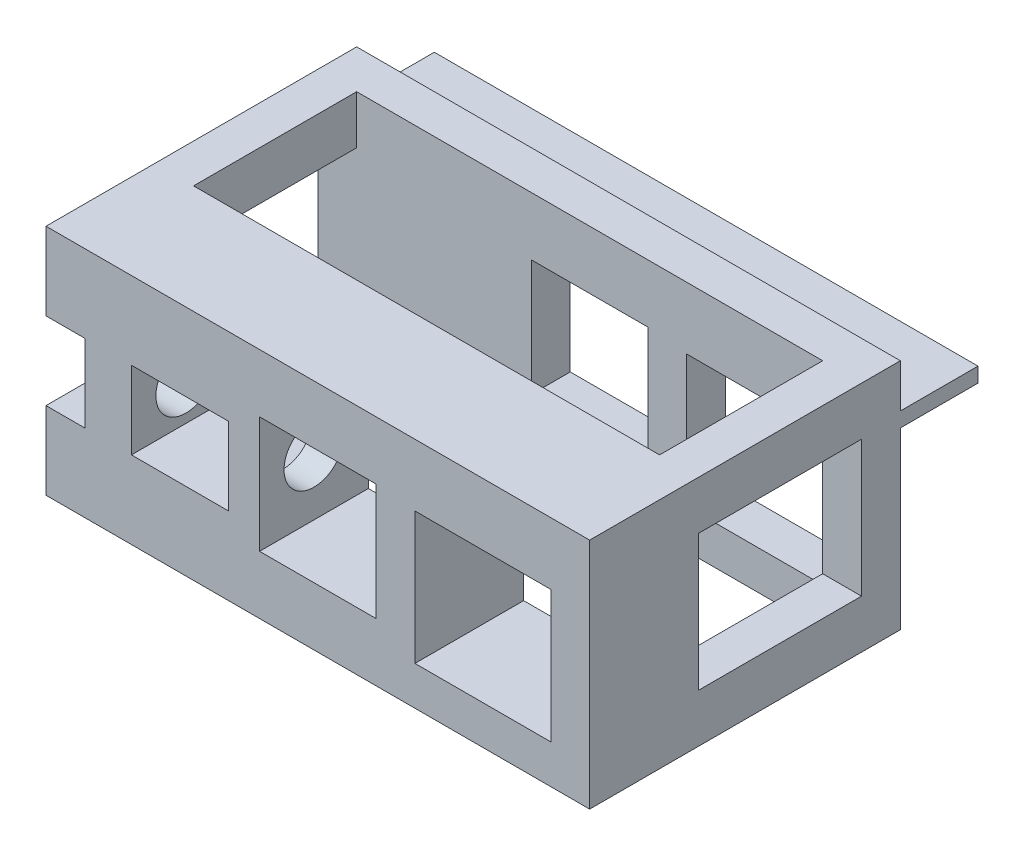
SolidWorks part; units mm, degrees
material "ABS"
ref_plane "Front Plane" through (0, 0, 0) normal (0, 0, 1) x (1, 0, 0)
ref_plane "Top Plane" through (0, 0, 0) normal (0, 1, 0) x (1, 0, 0)
ref_plane "Right Plane" through (0, 0, 0) normal (1, 0, 0) x (0, 0, -1)
sketch "Sketch1" plane through (0, 0, 0) normal (0, 0, 1) x (1, 0, 0)
  line L1 (0, 0) -> (88.9, 0)
  line L2 (0, 0) -> (0, 38.1)
  line L3 (0, 38.1) -> (88.9, 38.1)
  line L4 (88.9, 0) -> (88.9, 38.1)
  dimension "D1" = 88.9
  dimension "D2" = 38.1
extrude "Boss-Extrude1" add sketch "Sketch1" against normal blind 17.78
sketch "Sketch2" plane through (0, 0, 0) normal (0, 0, 1) x (1, 0, 0)
  line L0 (0, 19.05) -> (88.9, 19.05) construction
  line L1 (0, 0) -> (0, 38.1) construction
  line L2 (88.9, 0) -> (88.9, 38.1) construction
  line L3 (44.45, 0) -> (44.45, 38.1) construction
  line L4 (0, 0) -> (88.9, 0) construction
  line L5 (0, 38.1) -> (88.9, 38.1) construction
  line L6 (88.9, 30.1625) -> (82.55, 30.1625)
  line L7 (34.925, 28.575) -> (53.975, 28.575)
  line L8 (34.925, 28.575) -> (34.925, 9.525)
  line L9 (34.925, 9.525) -> (53.975, 9.525)
  line L10 (53.975, 28.575) -> (53.975, 9.525)
  line L11 (0, 39.0525) -> (6.35, 39.0525)
  line L12 (0, 39.0525) -> (0, 30.1625)
  line L13 (0, 30.1625) -> (6.35, 30.1625)
  line L14 (6.35, 39.0525) -> (6.35, 30.1625)
  line L15 (82.55, 39.0525) -> (82.55, 30.1625)
  line L16 (88.9, 39.0525) -> (82.55, 39.0525)
  line L17 (88.9, 39.0525) -> (88.9, 30.1625)
  line L18 (88.9, -0.9525) -> (88.9, 7.9375)
  line L19 (88.9, -0.9525) -> (82.55, -0.9525)
  line L20 (82.55, -0.9525) -> (82.55, 7.9375)
  line L21 (88.9, 7.9375) -> (82.55, 7.9375)
  line L22 (0, 7.9375) -> (6.35, 7.9375)
  line L23 (6.35, -0.9525) -> (6.35, 7.9375)
  line L24 (0, -0.9525) -> (6.35, -0.9525)
  line L25 (0, -0.9525) -> (0, 7.9375)
  line L26 (0, 38.1) -> (0, 0) construction
  line L27 (29.845, 25.4) -> (13.97, 25.4)
  line L28 (29.845, 25.4) -> (29.845, 12.7)
  line L29 (29.845, 12.7) -> (13.97, 12.7)
  line L30 (13.97, 25.4) -> (13.97, 12.7)
  dimension "D1" = 19.05
  dimension "D3" = 34.925
  dimension "D5" = 11.1125
  dimension "D6" = 8.89
  dimension "D7" = 6.35
  dimension "D10" = 12.7
  dimension "D2" = 19.05
  dimension "D4" = 9.525
  dimension "D11" = 6.35
  dimension "D9" = 13.97
  dimension "D8" = 5.08
extrude "Cut-Extrude1" cut sketch "Sketch2" against normal blind 41.402 contours L28 L27 L30 L29 | L8 L7 L10 L9 | L12 L11 L14 L13 | L22 L23 L24 L25 | L18 L21 L20 L19 | L6 L15 L16 L17
ref_plane "Plane1" through (0, 0, -50.8) normal (0, 0, 1) x (1, 0, 0)
sketch "Sketch3" plane through (0, 0, -50.8) normal (0, 0, 1) x (1, 0, 0)
  line L0 (34.925, 9.525) -> (53.975, 9.525) construction
  line L1 (53.975, 9.525) -> (53.975, 28.575) construction
  line L2 (53.975, 28.575) -> (34.925, 28.575) construction
  line L3 (34.925, 28.575) -> (34.925, 9.525) construction
  line L4 (34.925, 9.525) -> (53.975, 9.525)
  line L5 (53.975, 9.525) -> (53.975, 28.575)
  line L6 (53.975, 28.575) -> (34.925, 28.575)
  line L7 (34.925, 28.575) -> (34.925, 9.525)
  line L20 (88.9, 7.9375) -> (88.9, 30.1625)
  line L25 (82.55, 38.1) -> (6.35, 38.1)
  line L26 (0, 30.1625) -> (0, 7.9375)
  line L31 (88.9, 30.1625) -> (82.55, 30.1625)
  line L33 (88.9, 30.1625) -> (82.55, 30.1625)
  line L35 (6.35, 0) -> (82.55, 0)
  line L36 (82.55, 30.1625) -> (82.55, 38.1)
  line L38 (82.55, 30.1625) -> (82.55, 38.1)
  line L40 (88.9, 7.9375) -> (88.9, 30.1625)
  line L45 (82.55, 38.1) -> (6.35, 38.1)
  line L46 (0, 30.1625) -> (0, 7.9375)
  line L55 (6.35, 0) -> (82.55, 0)
  line L72 (6.35, 38.1) -> (6.35, 30.1625)
  line L76 (6.35, 38.1) -> (6.35, 30.1625)
  line L80 (6.35, 30.1625) -> (0, 30.1625)
  line L82 (6.35, 30.1625) -> (0, 30.1625)
  line L88 (0, 7.9375) -> (6.35, 7.9375)
  line L89 (0, 7.9375) -> (6.35, 7.9375)
  line L90 (6.35, 7.9375) -> (6.35, 0)
  line L91 (6.35, 7.9375) -> (6.35, 0)
  line L100 (82.55, 0) -> (82.55, 7.9375)
  line L101 (82.55, 0) -> (82.55, 7.9375)
  line L102 (82.55, 7.9375) -> (88.9, 7.9375)
  line L103 (82.55, 7.9375) -> (88.9, 7.9375)
  dimension "D1" = 0
extrude "Boss-Extrude2" add sketch "Sketch3" along normal blind 6.35
sketch "Sketch6" plane through (6.35, 0, 0) normal (-1, 0, 0) x (0, 0, 1)
  line L0 (-17.78, 38.1) -> (-17.78, 30.1625) construction
  line L6 (-17.78, 12.7) -> (0, 12.7)
  line L7 (0, 12.7) -> (0, 25.4)
  line L8 (0, 25.4) -> (-17.78, 25.4)
  line L9 (-17.78, 25.4) -> (-17.78, 12.7)
  line L10 (-17.78, 12.7) -> (0, 12.7)
  line L11 (0, 12.7) -> (0, 25.4)
  line L12 (0, 25.4) -> (-17.78, 25.4)
  line L13 (-17.78, 25.4) -> (-17.78, 12.7)
  circle A0 centre (-8.89, 19.05) radius 4.8895
  dimension "D2" = 9.779
  dimension "D1" = 8.89
  dimension "D5" = 12.7
  dimension "D3" = 6.35
extrude "SpringPlunger Hole" cut sketch "Sketch6" against normal up to surface and the other way up to surface contours A0 up to face at (34.925, 19.05, -8.89) other way up to face at (0, 19.05, -8.89)
sketch "Sketch8" plane through (0, 0, 0) normal (0, 0, 1) x (1, 0, 0)
  line L30 (0, 0) -> (0, 38.1) construction
  line L31 (0, 38.1) -> (6.35, 38.1)
  line L32 (0, 38.1) -> (0, 30.1625)
  line L33 (0, 30.1625) -> (6.35, 30.1625)
  line L34 (6.35, 38.1) -> (6.35, 30.1625)
  line L35 (82.55, 38.1) -> (88.9, 38.1)
  line L36 (82.55, 38.1) -> (82.55, 30.1625)
  line L37 (82.55, 30.1625) -> (88.9, 30.1625)
  line L38 (88.9, 38.1) -> (88.9, 30.1625)
  line L39 (82.55, 7.9375) -> (88.9, 7.9375)
  line L40 (82.55, 7.9375) -> (82.55, 0)
  line L41 (82.55, 0) -> (88.9, 0)
  line L42 (88.9, 7.9375) -> (88.9, 0)
  line L43 (0, 7.9375) -> (6.35, 7.9375)
  line L44 (0, 7.9375) -> (0, 0)
  line L45 (0, 0) -> (6.35, 0)
  line L46 (6.35, 7.9375) -> (6.35, 0)
  line L47 (0, 7.9375) -> (6.35, 7.9375) construction
  line L48 (0, 0) -> (88.9, 0) construction
  line L49 (6.35, 7.9375) -> (6.35, 0) construction
  line M10 (88.9, 30.1625) -> (82.55, 30.1625)
  line M11 (82.55, 30.1625) -> (82.55, 38.1)
  line M17 (6.35, 38.1) -> (6.35, 30.1625)
  line M18 (6.35, 30.1625) -> (0, 30.1625)
  line M20 (0, 7.9375) -> (6.35, 7.9375)
  line M21 (6.35, 7.9375) -> (6.35, 0)
  line M27 (82.55, 0) -> (82.55, 7.9375)
  line M28 (82.55, 7.9375) -> (88.9, 7.9375)
extrude "Support" add sketch "Sketch8" against normal up to surface (50.8 mm away) contours L31 L32 M18 M17 | L38 L35 M11 M10 | L42 L41 M28 M27 | L44 L45 M21 M20 up to face at (44.45, 19.05, -50.8)
extrude "Cut-Extrude2" cut sketch "Sketch6<3>" along normal up to surface (6.35 mm away) contours L12 L13 L10 L11 A0 | A0 region at (6.35, 19.05, -17.5615) region at (6.35, 19.05, -8.89) up to face at (0, 19.05, -25.4)
sketch "Sketch6<3>" plane through (6.35, 0, 0) normal (-1, 0, 0) x (0, 0, 1) same geometry as "Sketch6"
sketch "Sketch9" plane through (29.845, 0, 0) normal (-1, 0, 0) x (0, 0, 1)
  circle A3 centre (-8.89, 19.05) radius 4.8895
  dimension "D2" = 9.779
extrude "Cut-Extrude4" [suppressed] cut sketch "Sketch9" against normal up to surface (5.08 mm away) up to face at (34.925, 19.05, -4.0005)
sketch "Sketch10" plane through (0, 0, -50.8) normal (0, 0, -1) x (-1, 0, 0)
  line L0 (-88.9, 0) -> (-88.9, 38.1) construction
  line L1 (-88.9, 30.988) -> (0, 30.988)
  line L2 (-88.9, 30.988) -> (-88.9, 28.575)
  line L3 (-88.9, 28.575) -> (0, 28.575)
  line L4 (0, 30.988) -> (0, 28.575)
  line L5 (0, 38.1) -> (0, 0) construction
  line L6 (-88.9, 38.1) -> (0, 38.1) construction
  line L7 (-53.975, 28.575) -> (-34.925, 28.575) construction
  dimension "D1" = 7.112
extrude "Boss-Extrude3" add sketch "Sketch10" along normal blind 12.7
sketch "Sketch11" plane through (0, 0, 0) normal (0, 0, 1) x (1, 0, 0)
  line L0 (88.9, 0) -> (88.9, 38.1) construction
  line L1 (60.325, 27.94) -> (82.55, 27.94)
  line L2 (60.325, 27.94) -> (60.325, 6.35)
  line L3 (60.325, 6.35) -> (82.55, 6.35)
  line L4 (82.55, 27.94) -> (82.55, 6.35)
  line L5 (53.975, 28.575) -> (53.975, 9.525) construction
  line L6 (0, 38.1) -> (88.9, 38.1) construction
  line L7 (0, 0) -> (88.9, 0) construction
  dimension "D1" = 6.35
  dimension "D2" = 6.35
  dimension "D3" = 10.16
  dimension "D4" = 6.35
extrude "Cut-Extrude5" cut sketch "Sketch11" against normal up to surface (50.8 mm away) up to face at (44.45, 16.6687, -50.8)
equation "\"box\"= 3.5"
equation "\"D1@Sketch1\"=\"box\""
equation "\"shaft\"= .75"
equation "\"D1@Sketch2\"=\"shaft\""
equation "\"D3@Sketch2\"=(\"box\"-\"shaft\")/2"
equation "\"D5@Sketch2\"=\"box\"/8"
equation "\"D6@Sketch2\"=\"box\"/10"
equation "\"D7@Sketch2\"=0.25"
equation "\"springHole\"=1"
equation "\"depth1\"=0.7"
equation "\"D1@Boss-Extrude1\"=\"depth1\""
equation "\"D1@Sketch6\"=\"depth1\"/2"
equation "\"springShaftD\"=0.385"
equation "\"D2@Sketch6\"=\"springShaftD\""
equation "\"D2@Sketch1\"=(\"box\"/3.5)*1.5"
equation "\"D2@Sketch2\"=\"shaft\""
equation "\"D4@Sketch2\"=\"shaft\"/2"
equation "\"D11@Sketch2\"=\"D10@Sketch2\"/2"
equation "\"D3@Sketch6\"=\"D5@Sketch6\"/2"
equation "\"springPinD\"=0.385"
equation "\"D2@Sketch9\"=\"springPinD\""
